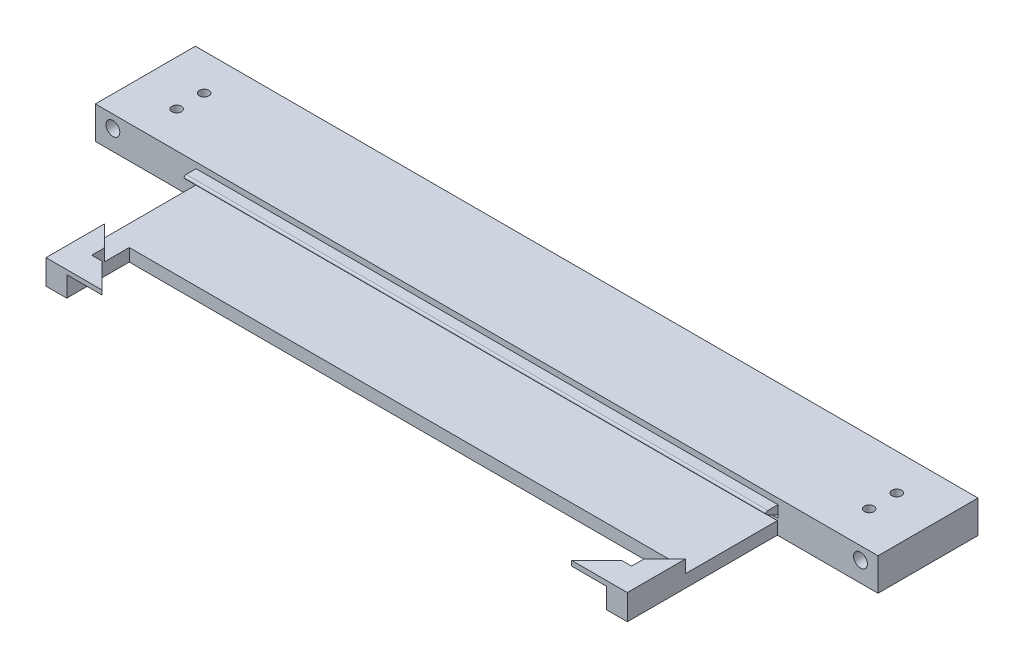
SolidWorks part; units mm, degrees
ref_plane "Front Plane" through (0, 0, 0) normal (0, 0, 1) x (1, 0, 0)
ref_plane "Top Plane" through (0, 0, 0) normal (0, 1, 0) x (1, 0, 0)
ref_plane "Right Plane" through (0, 0, 0) normal (1, 0, 0) x (0, 0, -1)
sketch "Sketch1" plane through (0, 0, 0) normal (1, 0, 0) x (0, 0, -1)
  line L1 (0, 0) -> (40, 0)
  line L2 (0, 0) -> (0, 10)
  line L3 (0, 10) -> (40, 10)
  line L4 (40, 0) -> (40, 10)
  dimension "D1" = 10
  dimension "D2" = 40
extrude "Boss-Extrude1" add sketch "Sketch1" along normal blind 312.998
sketch "Sketch2" plane through (0, 0, -40) normal (0, 0, -1) x (-1, 0, 0)
  line L1 (-272.994, 3) -> (-40.004, 3)
  line L2 (-272.994, 3) -> (-272.994, 4.2)
  line L3 (-272.994, 4.2) -> (-40.004, 4.2)
  line L4 (-40.004, 3) -> (-40.004, 4.2)
  line L5 (-272.994, 4.2) -> (-312.998, 0) construction
  line L6 (-40.004, 4.2) -> (0, 0) construction
  line L7 (-312.998, 0) -> (0, 0) construction
  dimension "D1" = 232.99
  dimension "D2" = 3
  dimension "D3" = 1.2
extrude "Cut-Extrude1" cut sketch "Sketch2" against normal through all
sketch "Sketch3" plane through (0, 10, 0) normal (0, 1, 0) x (1, 0, 0)
  line L0 (156.499, 71.4665) -> (156.499, -49.9307) construction
  line L1 (0, 40) -> (156.499, 71.4665) construction
  line L2 (156.499, 71.4665) -> (312.998, 40) construction
  line L3 (312.998, 40) -> (312.998, 0) construction
  line L4 (312.998, 40) -> (0, 40) construction
  line L5 (312.998, 40) -> (294.998, 25.5) construction
  line L6 (294.998, 25.5) -> (294.998, 14.5) construction
  line L7 (294.998, 14.5) -> (312.998, 0) construction
  circle A0 centre (294.998, 25.5) radius 1.9177
  circle A1 centre (294.998, 14.5) radius 1.9177
  circle A2 centre (18, 14.5) radius 1.9177
  circle A3 centre (18, 25.5) radius 1.9177
  dimension "D3" = 3.8354
  dimension "D1" = 18
  dimension "D2" = 14.5
extrude "Cut-Extrude2" cut sketch "Sketch3" against normal through all
sketch "Sketch4" plane through (0, 0, 0) normal (0, -1, 0) x (1, 0, 0)
  line L1 (14.5837, -12.5276) -> (14.5837, -16.4724)
  line L2 (14.5837, -16.4724) -> (18, -18.4448)
  line L3 (18, -18.4448) -> (21.4163, -16.4724)
  line L4 (21.4163, -16.4724) -> (21.4163, -12.5276)
  line L5 (21.4163, -12.5276) -> (18, -10.5552)
  line L6 (18, -10.5552) -> (14.5837, -12.5276)
  line L7 (14.5837, -23.5276) -> (14.5837, -27.4724)
  line L8 (14.5837, -27.4724) -> (18, -29.4448)
  line L9 (18, -29.4448) -> (21.4163, -27.4724)
  line L10 (21.4163, -27.4724) -> (21.4163, -23.5276)
  line L11 (21.4163, -23.5276) -> (18, -21.5552)
  line L12 (18, -21.5552) -> (14.5837, -23.5276)
  line L13 (298.4143, -12.5276) -> (294.998, -10.5552)
  line L14 (294.998, -10.5552) -> (291.5817, -12.5276)
  line L15 (291.5817, -12.5276) -> (291.5817, -16.4724)
  line L16 (291.5817, -16.4724) -> (294.998, -18.4448)
  line L17 (294.998, -18.4448) -> (298.4143, -16.4724)
  line L18 (298.4143, -16.4724) -> (298.4143, -12.5276)
  line L19 (291.5817, -23.5276) -> (291.5817, -27.4724)
  line L20 (291.5817, -27.4724) -> (294.998, -29.4448)
  line L21 (294.998, -29.4448) -> (298.4143, -27.4724)
  line L22 (298.4143, -27.4724) -> (298.4143, -23.5276)
  line L23 (298.4143, -23.5276) -> (294.998, -21.5552)
  line L24 (294.998, -21.5552) -> (291.5817, -23.5276)
  circle A0 centre (18, -14.5) radius 3.4163 construction
  circle A1 centre (18, -25.5) radius 3.4163 construction
  circle A2 centre (294.998, -14.5) radius 3.4163 construction
  circle A3 centre (294.998, -25.5) radius 3.4163 construction
  dimension "D1" = 6.8326
extrude "Cut-Extrude3" cut sketch "Sketch4" against normal blind 4.3
sketch "Sketch5" plane through (0, 0, 0) normal (0, 0, 1) x (1, 0, 0)
  line L0 (0, 10) -> (7, 5) construction
  line L1 (7, 5) -> (0, 0) construction
  line L2 (0, 10) -> (156.499, 87.0064) construction
  line L3 (156.499, 87.0064) -> (312.998, 10) construction
  line L4 (312.998, 10) -> (312.998, 0) construction
  line L5 (312.998, 10) -> (0, 10) construction
  line L6 (156.499, 87.0064) -> (156.499, -80.9825) construction
  line L7 (305.998, 5) -> (312.998, 0) construction
  line L8 (312.998, 10) -> (305.998, 5) construction
  circle A0 centre (7, 5) radius 2.7623
  circle A1 centre (305.998, 5) radius 2.7623
  dimension "D1" = 5.5245
  dimension "D2" = 7
extrude "Cut-Extrude4" cut sketch "Sketch5" against normal through all
sketch "Sketch6" plane through (0, 0, 0) normal (-1, 0, 0) x (0, 0, 1)
  line L0 (-40, 10) -> (-33, 8.4163) construction
  line L1 (-33, 8.4163) -> (-29.8453, 8.4163)
  line L2 (-33, 8.4163) -> (-33, 1.5837)
  line L3 (-33, 1.5837) -> (-29.8453, 1.5837)
  line L4 (-29.8453, 8.4163) -> (-29.8453, 1.5837)
  line L9 (-33, 1.5837) -> (-40, 0) construction
  line L10 (-40, 10) -> (-20, 18.9404) construction
  line L11 (-20, 18.9404) -> (0, 10) construction
  line L12 (-20, 18.9404) -> (-20, -7.3414) construction
  line L13 (-7, 1.5837) -> (0, 0) construction
  line L14 (0, 10) -> (-7, 8.4163) construction
  line L15 (-10.1547, 8.4163) -> (-10.1547, 1.5837)
  line L16 (-7, 1.5837) -> (-10.1547, 1.5837)
  line L17 (-7, 8.4163) -> (-7, 1.5837)
  line L18 (-7, 8.4163) -> (-10.1547, 8.4163)
  dimension "D1" = 7
  dimension "D2" = 3.1547
  dimension "D3" = 6.8326
extrude "Cut-Extrude5" cut sketch "Sketch6" against normal blind 15
ref_plane "Plane1" through (156.499, 0, 0) normal (-1, 0, 0) x (0, 0, 1)
sketch "Sketch7" plane through (0, 0, 0) normal (0, 0, 1) x (1, 0, 0)
  line L0 (312.998, 0) -> (0, 0) construction
  line L1 (40.249, 0) -> (272.749, 0)
  line L2 (40.249, 0) -> (40.249, 2.0463)
  line L3 (40.249, 2.0463) -> (272.749, 2.0463)
  line L4 (272.749, 0) -> (272.749, 2.0463)
  line L5 (40.249, 2.0463) -> (40.004, 4.2) construction
  line L6 (272.994, 4.2) -> (272.749, 2.0463) construction
  dimension "D1" = 232.5
extrude "Boss-Extrude2" add sketch "Sketch7" along normal blind 60
sketch "Sketch8" plane through (0, 2.0463, 0) normal (0, 1, 0) x (1, 0, 0)
  line L0 (272.749, -60) -> (40.249, -60) construction
  line L1 (48.549, -35) -> (264.449, -35)
  line L2 (48.549, -35) -> (48.549, -60)
  line L3 (48.549, -60) -> (264.449, -60)
  line L4 (264.449, -35) -> (264.449, -60)
  line L5 (48.549, -35) -> (40.249, -60) construction
  line L6 (272.749, -60) -> (264.449, -35) construction
  dimension "D1" = 25
  dimension "D2" = 215.9
extrude "Cut-Extrude6" cut sketch "Sketch8" against normal up to next
sketch "Sketch9" plane through (0, 0, 0) normal (0, -1, 0) x (1, 0, 0)
  line L0 (0, -40) -> (0, 0)
  line L1 (0, 0) -> (40.249, 0)
  line L2 (40.249, 0) -> (40.249, 60)
  line L3 (40.249, 60) -> (48.549, 60)
  line L4 (48.549, 60) -> (48.549, 35)
  line L5 (48.549, 35) -> (264.449, 35)
  line L6 (264.449, 35) -> (264.449, 60)
  line L7 (264.449, 60) -> (272.749, 60)
  line L8 (272.749, 60) -> (272.749, 0)
  line L9 (272.749, 0) -> (312.998, 0)
  line L10 (312.998, 0) -> (312.998, -40)
  line L11 (312.998, -40) -> (0, -40)
  line L12 (21.4163, -16.4724) -> (21.4163, -12.5276) construction
  line L13 (17.9977, -10.5552) -> (14.5825, -12.5296)
  line L14 (14.5825, -12.5296) -> (14.5849, -16.4744)
  line L15 (14.5849, -16.4744) -> (18.0023, -18.4448)
  line L16 (18.0023, -18.4448) -> (21.4175, -16.4704)
  line L17 (21.4175, -16.4704) -> (21.4151, -12.5256)
  line L18 (21.4151, -12.5256) -> (17.9977, -10.5552)
  line L19 (18.0023, -21.5552) -> (14.5849, -23.5256)
  line L20 (14.5849, -23.5256) -> (14.5825, -27.4704)
  line L21 (14.5825, -27.4704) -> (17.9977, -29.4448)
  line L22 (17.9977, -29.4448) -> (21.4151, -27.4744)
  line L23 (21.4151, -27.4744) -> (21.4175, -23.5296)
  line L24 (21.4175, -23.5296) -> (18.0023, -21.5552)
  line L25 (295.0003, -10.5552) -> (291.5828, -12.5256)
  line L26 (291.5828, -12.5256) -> (291.5805, -16.4704)
  line L27 (291.5805, -16.4704) -> (294.9956, -18.4448)
  line L28 (294.9956, -18.4448) -> (298.4131, -16.4744)
  line L29 (298.4131, -16.4744) -> (298.4154, -12.5296)
  line L30 (298.4154, -12.5296) -> (295.0003, -10.5552)
  line L31 (294.9956, -21.5552) -> (291.5805, -23.5296)
  line L32 (291.5805, -23.5296) -> (291.5828, -27.4744)
  line L33 (291.5828, -27.4744) -> (295.0003, -29.4448)
  line L34 (295.0003, -29.4448) -> (298.4154, -27.4704)
  line L35 (298.4154, -27.4704) -> (298.4131, -23.5256)
  line L36 (298.4131, -23.5256) -> (294.9956, -21.5552)
  circle A0 centre (18, -14.5) radius 3.4163 construction
  circle A1 centre (18, -25.5) radius 3.4163 construction
  circle A2 centre (294.998, -14.5) radius 3.4163 construction
  circle A3 centre (294.998, -25.5) radius 3.4163 construction
extrude "Boss-Extrude3" add sketch "Sketch9" along normal blind 3
sketch "Sketch10" plane through (40.249, 0, 0) normal (-1, 0, 0) x (0, 0, 1)
  line L1 (60, 2.0463) -> (35, 2.0463)
  line L2 (60, 2.0463) -> (60, 6.8906)
  line L3 (60, 6.8906) -> (35, 6.8906)
  line L4 (35, 2.0463) -> (35, 6.8906)
  dimension "D1" = 25
extrude "Boss-Extrude4" add sketch "Sketch10" against normal up to surface (8.3 mm away) up to face at (48.549, -0.4768, 47.5)
sketch "Sketch11" plane through (48.549, 0, 0) normal (1, 0, 0) x (0, 0, -1)
  line L0 (-60, 2.0463) -> (0, 2.0463) construction
  line L1 (-60, 6.8906) -> (-50, 6.8906)
  line L2 (-60, 6.8906) -> (-60, 2.0463)
  line L3 (-60, 2.0463) -> (-50, 2.0463)
  line L4 (-50, 6.8906) -> (-50, 2.0463)
  dimension "D1" = 10
extrude "Boss-Extrude5" add sketch "Sketch11" along normal blind 14
sketch "Sketch12" plane through (40.249, 0, 0) normal (-1, 0, 0) x (0, 0, 1)
  line L4 (0, 4.2) -> (7, 7.7)
  line L5 (7, 7.7) -> (0, 7.7)
  line L6 (0, 7.7) -> (0, 4.2)
  line L7 (0, 10) -> (0, -3) construction
  dimension "D1" = 7
  dimension "D2" = 3.5
extrude "Boss-Extrude6" add sketch "Sketch12" against normal up to surface (232.745 mm away) up to face at (272.994, 3.6, -20)
fillet "Fillet1" radius 0.7 1 edges at (156.6215, 7.7, 7)
sketch "Sketch13" plane through (0, 2.0463, 0) normal (0, 1, 0) x (1, 0, 0)
  line L0 (62.549, -50) -> (62.549, -60) construction
  line L2 (272.749, -60) -> (272.749, -35)
  line L3 (272.749, -35) -> (264.449, -35)
  line L4 (264.449, -50) -> (264.449, -35)
  line L7 (264.449, -50) -> (250.449, -50)
  line L8 (250.449, -60) -> (250.449, -50)
  line L9 (250.449, -60) -> (272.749, -60)
  line L10 (62.549, -60) -> (40.249, -60) construction
extrude "Boss-Extrude7" add sketch "Sketch13" along normal blind 5.0897
chamfer "Chamfer1" distance 10 angle 45 4 edges at (48.549, 4.4685, 35) (62.549, 4.4685, 50) (250.449, 4.5911, 50) (264.449, 4.5911, 35)
sketch "Sketch14" plane through (0, 2.0463, 0) normal (0, -1, 0) x (1, 0, 0)
  line L1 (48.549, 60) -> (264.449, 60)
  line L2 (48.549, 60) -> (48.549, 50)
  line L3 (48.549, 50) -> (264.449, 50)
  line L4 (264.449, 60) -> (264.449, 50)
extrude "Cut-Extrude7" cut sketch "Sketch14" against normal blind 3.1
